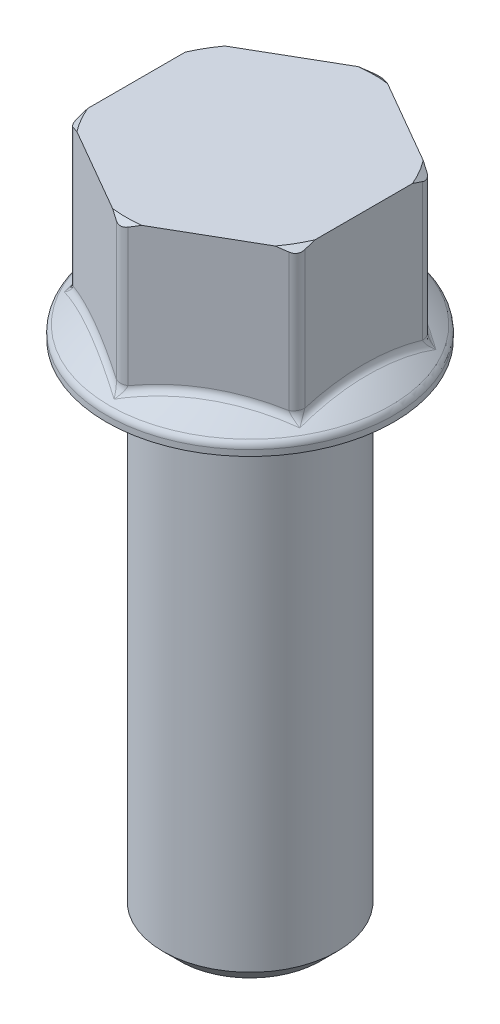
SolidWorks part; units mm, degrees
ref_plane "Front Plane" through (0, 0, 0) normal (0, 0, 1) x (1, 0, 0)
ref_plane "Top Plane" through (0, 0, 0) normal (0, 1, 0) x (1, 0, 0)
ref_plane "Right Plane" through (0, 0, 0) normal (1, 0, 0) x (0, 0, -1)
sketch "Sketch1" plane through (0, 0, 0) normal (0, 1, 0) x (1, 0, 0)
  circle A0 centre (0, 0) radius 4.3
extrude "Extrude1" add sketch "Sketch1" along normal blind 0.3
dome "Dome1" faces to dome 1 distance 1.5 reverse direction no elliptical dome no face at (0, 0.3, 4.3) parameters "D1"=1.5
ref_plane "Plane1" through (0, 5, 0) normal (0, -1, 0) x (1, 0, 0)
sketch "Sketch2" plane through (0, 5, 0) normal (0, -1, 0) x (1, 0, 0)
  line L1 (0, 3.926) -> (-3.4, 1.963)
  line L2 (-3.4, 1.963) -> (-3.4, -1.963)
  line L3 (-3.4, -1.963) -> (0, -3.926)
  line L4 (0, -3.926) -> (3.4, -1.963)
  line L5 (3.4, -1.963) -> (3.4, 1.963)
  line L6 (3.4, 1.963) -> (0, 3.926)
  circle A0 centre (0, 0) radius 3.4 construction
extrude "Extrude2" add sketch "Sketch2" along normal up to next
sketch "Sketch10" plane through (0, 5, 0) normal (0, 1, 0) x (1, 0, 0)
  circle A0 centre (0, 0) radius 3.7
extrude "Extrude4" cut sketch "Sketch10" against normal blind 3 draft 52 flip side to cut
sketch "Sketch11" plane through (0, 0, 0) normal (0, -1, 0) x (1, 0, 0)
  circle A0 centre (0, 0) radius 3.5
extrude "Extrude5" add sketch "Sketch11" along normal blind 0.06
sketch "Sketch12" plane through (0, -0.06, 0) normal (0, -1, 0) x (1, 0, 0)
  circle A0 centre (0, 0) radius 2.6
extrude "Extrude6" add sketch "Sketch12" along normal blind 15
chamfer "Chamfer1" distance 0.5 angle 45 1 edges at (0, -15.06, -2.6)
fillet "Fillet1" radius 0.25 7 edges at (1.7, 0.9061, -2.9445) (-1.7, 0.9061, -2.9445) (-3.4, 0.9061, 0) (-1.7, 0.9061, 2.9445) (1.7, 0.9061, 2.9445) (3.4, 0.9061, 0) (0, 0.3, 4.3)
fillet "Fillet2" radius 0.35 12 edges at (0, 0.6378, 3.9428) (-3.4146, 0.6378, 1.9714) (-3.4146, 0.6378, -1.9714) (0, 0.6378, -3.9428) (3.4146, 0.6378, -1.9714) (3.4146, 0.6378, 1.9714) (0, 2.7764, 3.926) (-3.4, 2.7764, 1.963) (-3.4, 2.7764, -1.963) (0, 2.7764, -3.926) (3.4, 2.7764, -1.963) (3.4, 2.7764, 1.963)
